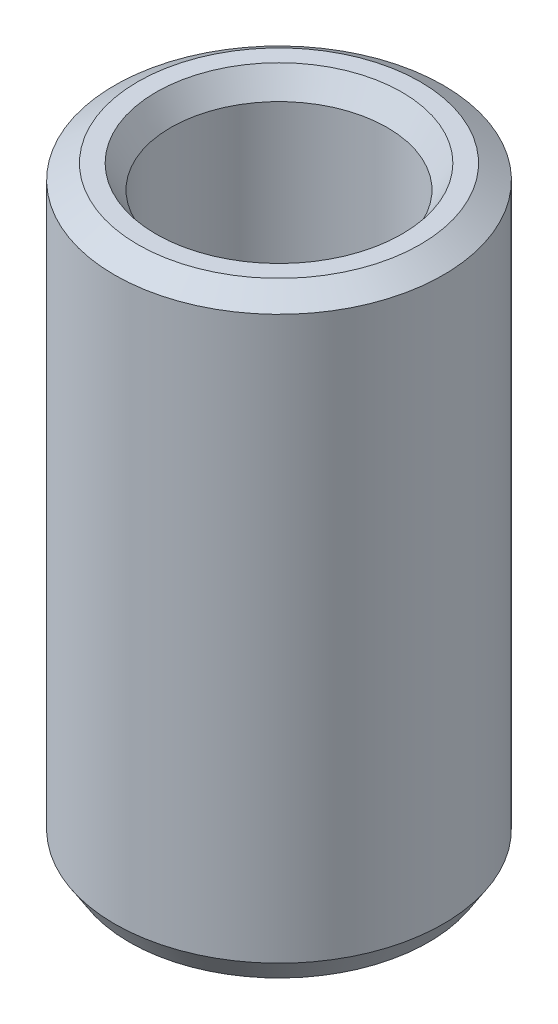
SolidWorks part; units mm, degrees
ref_plane "Front Plane" through (0, 0, 0) normal (0, 0, 1) x (1, 0, 0)
ref_plane "Top Plane" through (0, 0, 0) normal (0, 1, 0) x (1, 0, 0)
ref_plane "Right Plane" through (0, 0, 0) normal (1, 0, 0) x (0, 0, -1)
sketch "Sketch1" plane through (0, 0, 0) normal (0, 1, 0) x (1, 0, 0)
  circle A0 centre (0, 0) radius 17.5
  dimension "SLEEVE_OD" = 35
extrude "Boss-Extrude1" add sketch "Sketch1" along normal blind 63.8823
sketch "Sketch2" plane through (0, 0, 0) normal (0, 1, 0) x (1, 0, 0)
  circle A0 centre (0, 0) radius 11.5219
  dimension "BORE_D" = 23.0437
extrude "Cut-Extrude1" cut sketch "Sketch2" along normal through all
chamfer "Chamfer1" distance 1.5708 angle 57.569 4 edges at (0, 63.8823, 11.5219) (0, 0, 11.5219) (0, 0, 17.5) (0, 63.8823, 17.5) first distance on face at (0, 63.8823, 11.5219) first distance on face at (0, 0, 11.5219) first distance on face at (0, 63.8823, 17.5)
